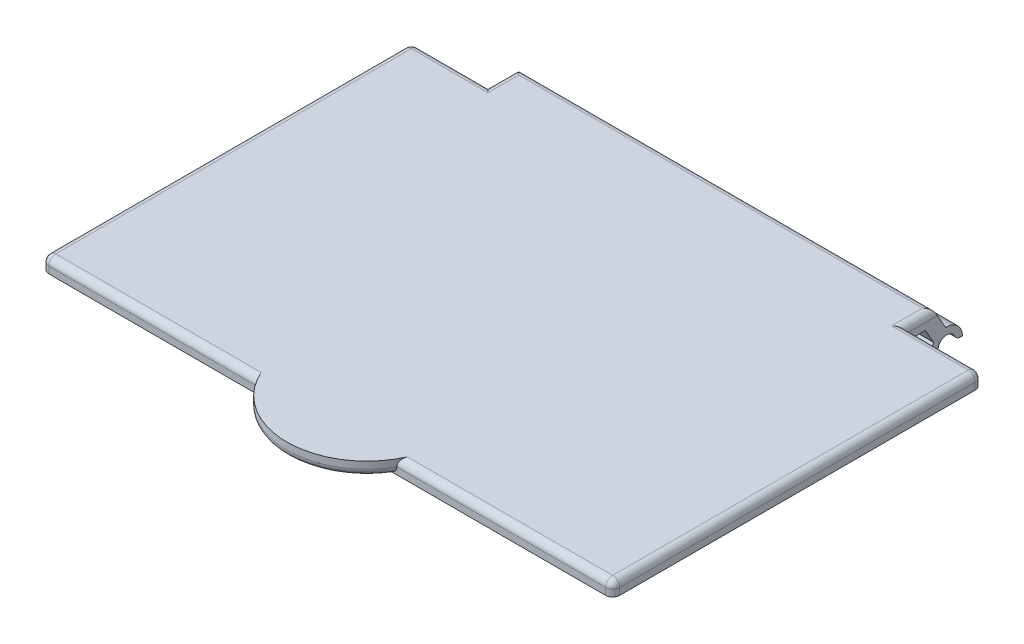
SolidWorks part; units mm, degrees
ref_plane "Front Plane" through (0, 0, 0) normal (0, 0, 1) x (1, 0, 0)
ref_plane "Top Plane" through (0, 0, 0) normal (0, 1, 0) x (1, 0, 0)
ref_plane "Right Plane" through (0, 0, 0) normal (1, 0, 0) x (0, 0, -1)
sketch "Sketch2" plane through (0, 0, 0) normal (1, 0, 0) x (0, 0, -1)
  line L0 (0, 0) -> (-2.5, 4.3301) construction
  line L10 (-2.5, 4.3301) -> (-59, 4.3301) construction
  line L11 (-0.1418, 2.2455) -> (-1.9226, 5.3301)
  line L12 (-1.9226, 5.3301) -> (-59, 5.3301)
  line L13 (-1.8738, 1.2455) -> (-3.0774, 3.3301)
  line L14 (-3.0774, 3.3301) -> (-59, 3.3301)
  line L16 (-59, 5.3301) -> (-59, 3.3301)
  line L17 (0, -1.25) -> (0, -2.25)
  line L18 (-0.866, -0.5) -> (-3.0774, 3.3301) construction
  line L19 (0.866, 0.5) -> (-1.9226, 5.3301) construction
  line L20 (1.25, 0) -> (2.25, 0)
  arc A1 (1.25, 0) -> (0, -1.25) centre (0, 0) ccw
  arc A2 (-1.8738, 1.2455) -> (0, -2.25) centre (0, 0) ccw
  arc A3 (2.25, 0) -> (-0.1418, 2.2455) centre (0, 0) ccw
  point P3 (0, 1)
  point P5 (-83.0274, 10.1443)
  point P6 (0, -1)
  point P7 (-83.0274, 10.1443)
  dimension "D9" = 2.5
  dimension "D1" = 4.5
  dimension "D2" = 60
  dimension "D3" = 59
  dimension "D4" = 5
  dimension "D5" = 1
  dimension "D6" = 1
extrude "Boss-Extrude1" add sketch "Sketch2" against normal mid plane 82
sketch "Sketch4" plane through (41, 0, 0) normal (1, 0, 0) x (0, 0, -1)
  line L0 (-3.0774, 3.3301) -> (-1.8738, 1.2455)
  line L3 (-1.9226, 5.3301) -> (-5.9226, 5.3301)
  line L4 (-1.9226, 5.3301) -> (-59, 5.3301) construction
  line L5 (-5.9226, 5.3301) -> (-5.9226, 3.3301)
  line L6 (-59, 3.3301) -> (-3.0774, 3.3301) construction
  line L7 (-5.9226, 3.3301) -> (-3.0774, 3.3301)
  line L8 (-1.9226, 5.3301) -> (-0.1418, 2.2455)
  line L14 (0, -2.25) -> (0, -1.25)
  line L15 (1.25, 0) -> (2.25, 0)
  line L16 (0, -2.25) -> (0, -1.25)
  line L17 (1.25, 0) -> (2.25, 0)
  arc A2 (-1.8738, 1.2455) -> (0, -2.25) centre (0, 0) ccw
  arc A3 (-1.8738, 1.2455) -> (0, -2.25) centre (0, 0) ccw
  arc A12 (1.25, 0) -> (0, -1.25) centre (0, 0) ccw
  arc A13 (2.25, 0) -> (-0.1418, 2.2455) centre (0, 0) ccw
  arc A14 (1.25, 0) -> (0, -1.25) centre (0, 0) ccw
  arc A15 (2.25, 0) -> (-0.1418, 2.2455) centre (0, 0) ccw
  dimension "D2" = 4
  dimension "D1" = 0
  dimension "D3" = 0
extrude "Cut-Extrude1" cut sketch "Sketch4" against normal blind 11
ref_plane "Plane1" through (0, 0, 0) normal (1, 0, 0) x (0, 0, -1)
mirror "Mirror1" about plane through (0, 0, 0) normal (1, 0, 0) of "Cut-Extrude1"
sketch "Sketch8" plane through (0, 5.3301, 0) normal (0, 1, 0) x (1, 0, 0)
  line L0 (0, -59) -> (-9.9973, -59)
  line L1 (-41, -59) -> (41, -59) construction
  line L2 (0, -59) -> (9.9973, -59)
  line L3 (0, -3.732) -> (0, 3.732) construction
  arc A1 (9.9973, -59) -> (-9.9973, -59) centre (0, -53.3164) cw
  dimension "D2" = 11.5
  dimension "D1" = 9.9973
extrude "Boss-Extrude4" add sketch "Sketch8" against normal up to surface (2 mm away) up to face at (0, 3.3301, 18.4807)
fillet "Fillet1" radius 1 16 edges at (-35.5, 5.3301, 5.9226) (35.5, 5.3301, 5.9226) (41, 4.3301, 59) (-41, 4.3301, 59) (41, 5.3301, 32.4613) (25.4987, 5.3301, 59) (-41, 5.3301, 32.4613) (-25.4987, 5.3301, 59) (41, 4.3301, 5.9226) (-41, 4.3301, 5.9226) (30, 5.3301, 3.9226) (-30, 5.3301, 3.9226) (0, 5.3301, 1.9226) (0, 3.3301, 64.8164) (0, -1.25, 0) (0, 0, -1.25)
equation "\"H\"= 3"
equation "\"L\"= 59"
equation "\"D3@Sketch2\"=\"L\""
equation "\"B\"=82"
equation "\"D1@Boss-Extrude1\"=\"B\""
